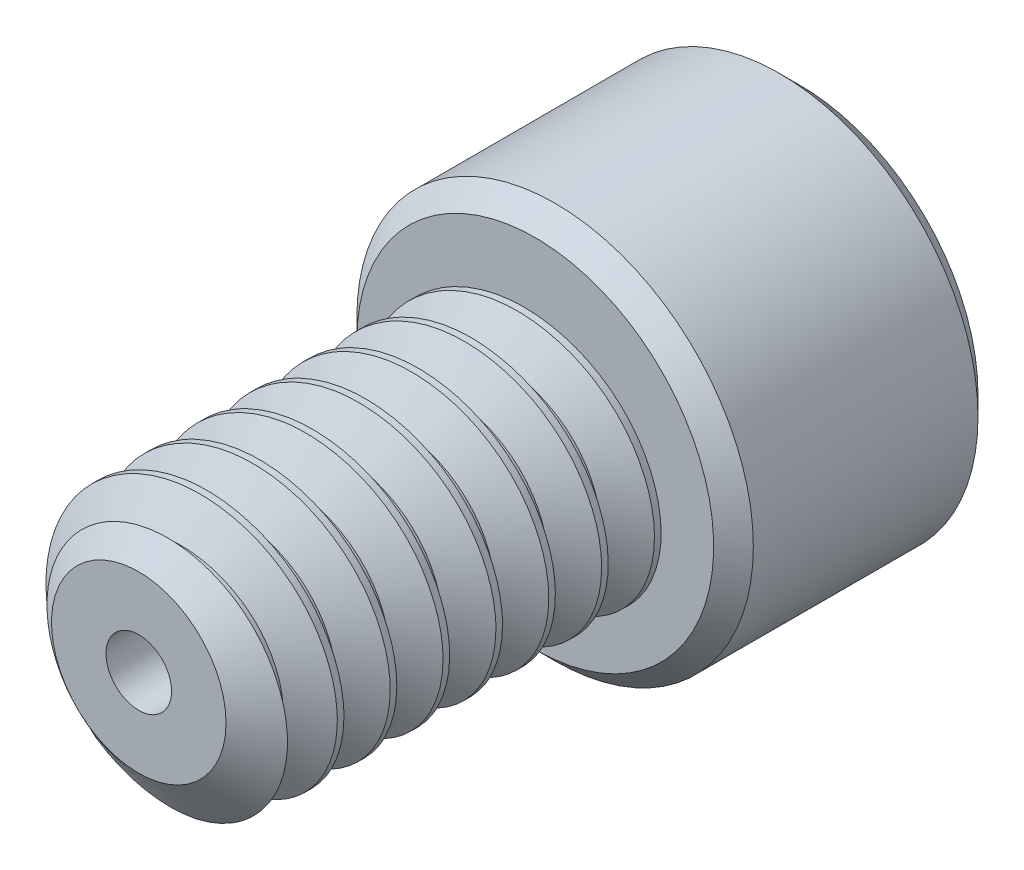
SolidWorks part; units mm, degrees
note: '?' marks a value the reader was unsure of.
ref_plane "Front Plane" through (0, 0, 0) normal (0, 0, 1) x (1, 0, 0)
ref_plane "Top Plane" through (0, 0, 0) normal (0, 1, 0) x (1, 0, 0)
ref_plane "Right Plane" through (0, 0, 0) normal (1, 0, 0) x (0, 0, -1)
sketch "Sketch1" plane through (0, 0, 0) normal (0, 0, 1) x (1, 0, 0)
  circle A0 centre (0, 0) radius 3.175
  dimension "OD" = 6.35
extrude "Extrude1" add sketch "Sketch1" against normal blind 9.525
sketch "Sketch2" plane through (0, 0, 0) normal (0, 0, 1) x (1, 0, 0)
  circle A0 centre (0, 0) radius 3.175 construction
  circle A1 centre (0, 0) radius 3.175
curve "Helix/Spiral1" pitch 1.27 height 10.795 turns 8.5 parameters "pitch"=1.27
sketch "Sketch3" plane through (0, 0, 0) normal (1, 0, 0) x (0, 0, -1)
  line L0 (-1.1113, 3.175) -> (-0.635, 2.3501)
  line L1 (-0.635, 2.3501) -> (-0.4762, 2.3501)
  line L2 (-0.4762, 2.3501) -> (0, 3.175)
  line L3 (-1.1113, 3.175) -> (0, 3.175)
  line L4 (-0.5556, 3.175) -> (-0.5556, 2.3501) construction
  line L5 (-0.8731, 2.7626) -> (-0.2381, 2.7626) construction
  line L6 (0, 3.175) -> (0, -3.175) construction
  dimension "D1" = 0.1588
  dimension "D2" = 0.635
  dimension "D3" = 60
sweep "Cut-Sweep1" cut profiles "Sketch3" path "Helix/Spiral1"
sketch "Sketch4" plane through (0, 0, 0) normal (1, 0, 0) x (0, 0, -1)
  line L0 (0.7554, 3.175) -> (0, 2.0961)
  line L1 (0, 2.0961) -> (0, 3.175)
  line L2 (0.7554, 3.175) -> (0, 3.175)
  line L3 (-1.1113, 3.175) -> (0, 3.175) construction
  line L4 (0, 0) -> (7.0209, 0) construction
  dimension "D1" = 55
  dimension "D2" = 0.254
revolve "Cut-Revolve1" cut sketch "Sketch4" angle 360 about L4
sketch "Sketch6" plane through (0, 0, -9.525) normal (0, 0, -1) x (-1, 0, 0)
  circle A0 centre (0, 0) radius 4.7625
  dimension "head dia" = 9.525
extrude "Extrude2" add sketch "Sketch6" along normal blind 6.35
sketch "Sketch7" plane through (0, 0, -15.875) normal (0, 0, -1) x (-1, 0, 0)
  line L1 (0, 2.7496) -> (-2.3813, 1.3748)
  line L2 (-2.3813, 1.3748) -> (-2.3813, -1.3748)
  line L3 (-2.3813, -1.3748) -> (0, -2.7496)
  line L4 (0, -2.7496) -> (2.3813, -1.3748)
  line L5 (2.3813, -1.3748) -> (2.3813, 1.3748)
  line L6 (2.3813, 1.3748) -> (0, 2.7496)
  circle A0 centre (0, 0) radius 2.3813 construction
  dimension "hex dia" = 4.7625
extrude "Cut-Extrude1" cut sketch "Sketch7" against normal blind 3.5719
sketch "Sketch8" plane through (0, 0, -15.875) normal (0, 0, -1) x (-1, 0, 0)
  circle A0 centre (0, 0) radius 2.7496
extrude "Cut-Extrude2" cut sketch "Sketch8" against normal through all draft 45
chamfer "Chamfer1" distance 0.4763 angle 45 2 edges at (-4.7625, 0, -15.875) (-4.7625, 0, -9.525)
sketch "Sketch10" plane through (0, 0, -9.525) normal (0, 0, 1) x (1, 0, 0)
  circle A1 centre (0, 0) radius 3.175
  circle A2 centre (0, 0) radius 3.175
  dimension "D1" = 0
ref_plane "Plane1" through (0, 0, 0) normal (0, 0, 1) x (1, 0, 0)
extrude "partial thread" [suppressed] add sketch "Sketch10" along normal up to surface (4.7625 mm away) separate body
chamfer "Chamfer2" [suppressed] distance 0.127 angle 45
combine bodies "Combine1" [suppressed] operation type? add bodies to combine 107 108
sketch "Sketch9" plane through (0, 0, 0) normal (1, 0, 0) x (0, 0, -1)
  line L0 (0, 3.175) -> (0, -3.175) construction
  line L1 (3.175, 3.175) -> (3.175, -3.175) construction
  dimension "D1" = 3.175
sketch "Sketch11" plane through (0, 0, 0) normal (0, 0, 1) x (1, 0, 0)
  circle A0 centre (0, 0) radius 0.7874
  dimension "Vent Dia" = 1.5748
extrude "Cut-Extrude3" cut sketch "Sketch11" against normal through all
equation "\"D3@Helix/Spiral1\" = \"screw length@Extrude1\"+\"pitch@Helix/Spiral1\""
equation "\"D1@Sketch3\" = \"pitch@Helix/Spiral1\"*.125"
equation "\"D2@Sketch3\" = \"pitch@Helix/Spiral1\"*.5"
equation "\"D1@Cut-Extrude1\" = \"hex dia@Sketch7\"*.75"
equation "\"D1@Chamfer1\" = \"head dia@Sketch6\"*.05"
equation "\"D1@Sketch9\" = \"pitch@Helix/Spiral1\"*2.5"
equation "\"D1@Chamfer2\"=\"OD@Sketch1\"*.02"
